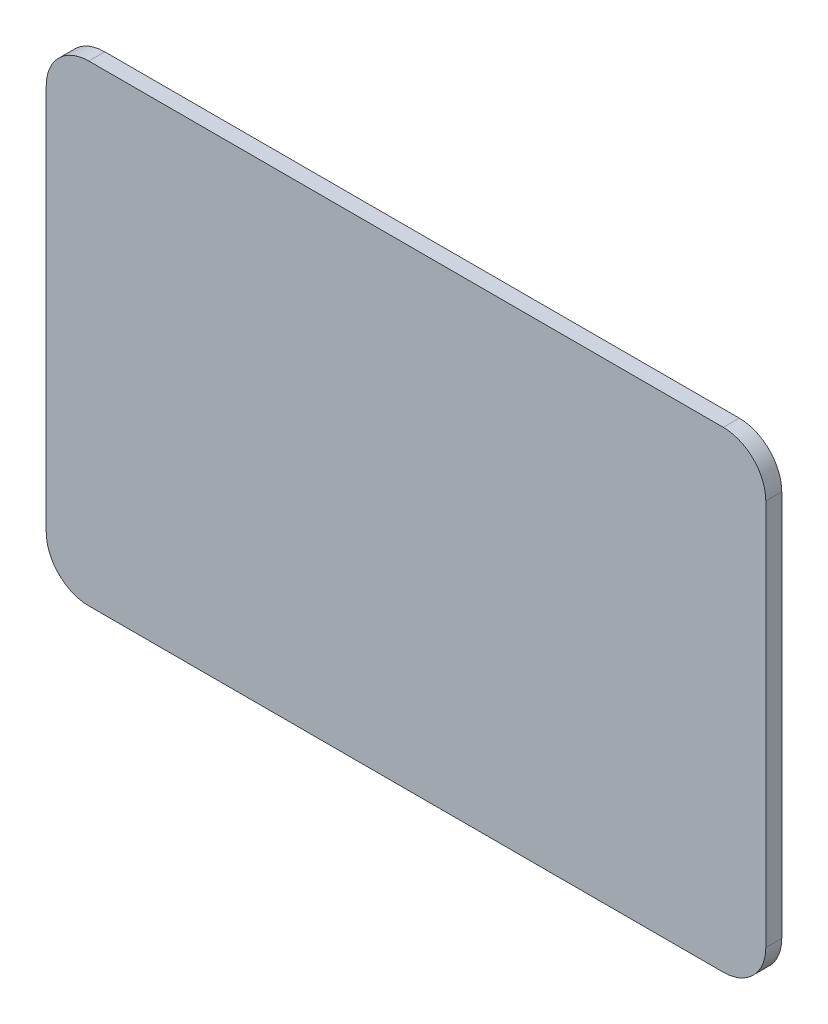
SolidWorks part; units mm, degrees
material "PC High Viscosity"
ref_plane "Front Plane" through (0, 0, 0) normal (0, 0, 1) x (1, 0, 0)
ref_plane "Top Plane" through (0, 0, 0) normal (0, 1, 0) x (1, 0, 0)
ref_plane "Right Plane" through (0, 0, 0) normal (1, 0, 0) x (0, 0, -1)
sketch "Sketch1" plane through (0, 0, 0) normal (0, 0, 1) x (1, 0, 0)
  line L3 (270.5, 171.4) -> (270.5, 26)
  line L4 (270.5, 26) -> (270.5, 171.4) construction
  line L5 (254.5, 10) -> (16, 10)
  line L6 (0, 26) -> (0, 171.4)
  line L7 (16, 187.4) -> (254.5, 187.4)
  arc A2 (254.5, 187.4) -> (270.5, 171.4) centre (254.5, 171.4) cw
  arc A3 (270.5, 171.4) -> (254.5, 187.4) centre (254.5, 171.4) ccw construction
  arc A4 (254.5, 10) -> (270.5, 26) centre (254.5, 26) ccw construction
  arc A5 (270.5, 26) -> (254.5, 10) centre (254.5, 26) cw
  arc A6 (16, 10) -> (0, 26) centre (16, 26) cw
  arc A7 (0, 171.4) -> (16, 187.4) centre (16, 171.4) cw
extrude "Boss-Extrude1" add sketch "Sketch1" along normal blind 6
